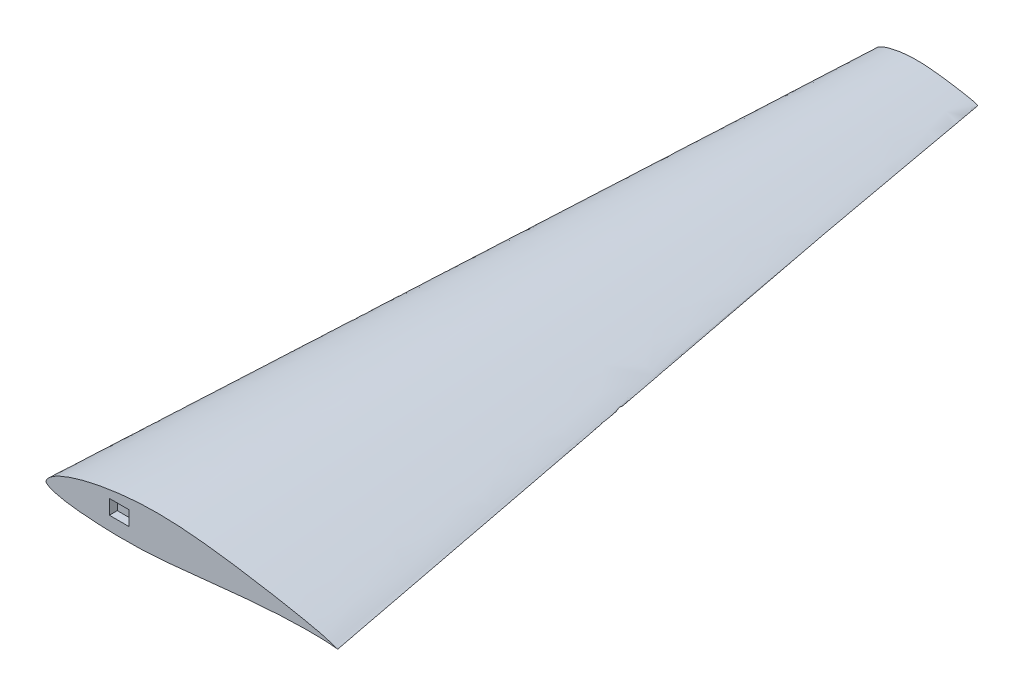
SolidWorks part; units mm, degrees
ref_plane "Front Plane" through (0, 0, 0) normal (0, 0, 1) x (1, 0, 0)
ref_plane "Top Plane" through (0, 0, 0) normal (0, 1, 0) x (1, 0, 0)
ref_plane "Right Plane" through (0, 0, 0) normal (1, 0, 0) x (0, 0, -1)
curve "Curve1"
  spline degree 3 poles (0.9921, 0.0008, 0) (1.0019, -0.0008, 0) (0.9929, 0.0016, 0) (0.9861, 0.0043, 0) (0.9706, 0.0096, 0) (0.9519, 0.0152, 0) (0.9278, 0.021, 0) (0.8992, 0.0273, 0) (0.8662, 0.0341, 0) (0.8293, 0.0413, 0) (0.789, 0.0488, 0) (0.746, 0.0564, 0) (0.7007, 0.0641, 0) (0.6538, 0.0714, 0) (0.6058, 0.0784, 0) (0.5573, 0.0846, 0) (0.5088, 0.0898, 0) (0.4609, 0.0938, 0) (0.4138, 0.0961, 0) (0.3679, 0.0966, 0) (0.3232, 0.0952, 0) (0.2801, 0.092, 0) (0.2388, 0.0874, 0) (0.1997, 0.0815, 0) (0.1631, 0.0746, 0) (0.1296, 0.0669, 0) (0.0993, 0.0585, 0) (0.0726, 0.0496, 0) (0.0499, 0.0404, 0) (0.0312, 0.031, 0) (0.0168, 0.0217, 0) (0.0085, 0.0145, 0) (0.0039, 0.009, 0) (0.0018, 0.0058, 0) (0.0004, 0.0024, 0) (0, 0.0003, 0) (0, -0.0012, 0) (0.0006, -0.0026, 0) (0.002, -0.0043, 0) (0.0049, -0.007, 0) (0.0107, -0.0108, 0) (0.0215, -0.0156, 0) (0.0378, -0.0206, 0) (0.0598, -0.0253, 0) (0.0864, -0.0294, 0) (0.1174, -0.033, 0) (0.1523, -0.036, 0) (0.1908, -0.0383, 0) (0.2323, -0.0397, 0) (0.2764, -0.0402, 0) (0.3228, -0.0395, 0) (0.3711, -0.0373, 0) (0.4212, -0.0335, 0) (0.4729, -0.0284, 0) (0.526, -0.0227, 0) (0.5798, -0.0169, 0) (0.6336, -0.0114, 0) (0.6866, -0.0064, 0) (0.7378, -0.0023, 0) (0.7866, 0.0009, 0) (0.832, 0.0031, 0) (0.8733, 0.0042, 0) (0.9096, 0.0045, 0) (0.9406, 0.0038, 0) (0.9645, 0.0029, 0) (0.984, 0.0013, 0) (0.9921, 0.0008, 0) (1.0019, -0.0008, 0) (0.9929, 0.0016, 0) knots -0.016161 -0.007282 -0.001839 0 0.00178 0.006777 0.014308 0.024046 0.036116 0.050547 0.06713 0.085624 0.105767 0.127282 0.149864 0.17323 0.197069 0.221103 0.245052 0.268663 0.291773 0.314299 0.336178 0.357377 0.377792 0.397225 0.415489 0.432417 0.447849 0.461651 0.473687 0.483898 0.492263 0.498797 0.499955 0.502811 0.504371 0.50536 0.505925 0.506503 0.507535 0.509205 0.512345 0.517665 0.526422 0.537425 0.550643 0.565966 0.583206 0.602155 0.622587 0.644255 0.666998 0.690703 0.715307 0.740824 0.767084 0.793717 0.820331 0.846519 0.871863 0.895937 0.918335 0.938667 0.956573 0.971715 0.983839 0.992718 0.998161 1 1.00178 1.006777 1.014308 periodic
sketch "Sketch1" plane through (0, 0, 0) normal (0, 0, 1) x (1, 0, 0)
  line L0 (1122.2059, -30.8288) -> (-1162.7941, -35.0845) construction
  spline S1 degree 3 poles (1104.1363, -28.0222) (1126.6295, -31.7875) (1105.8826, -26.3024) (1090.4575, -20.1288) (1054.9513, -7.9956) (1012.296, 4.6638) (957.0478, 17.8508) (891.7164, 32.0367) (816.2153, 47.3864) (731.9108, 63.6705) (639.9041, 80.612) (541.5101, 97.9168) (438.0076, 115.0958) (330.7593, 131.7488) (221.0675, 147.3336) (110.2357, 161.251) (-0.493, 172.9975) (-110.0556, 181.8587) (-217.6516, 186.9061) (-322.6724, 187.859) (-424.6755, 184.4831) (-523.1626, 176.9995) (-617.5035, 166.1709) (-706.8843, 152.6667) (-790.3524, 136.737) (-867.0563, 118.889) (-936.2082, 99.5088) (-997.0691, 79.0242) (-1049.0447, 57.9028) (-1091.6336, 36.4479) (-1124.4686, 15.1943) (-1143.3869, -1.4067) (-1153.8659, -14.0298) (-1158.6984, -21.3016) (-1161.9612, -29.0988) (-1162.8988, -33.8887) (-1162.7223, -37.2464) (-1161.3764, -40.4052) (-1158.2301, -44.4654) (-1151.5185, -50.6376) (-1138.2079, -59.2164) (-1113.635, -70.0567) (-1076.2399, -81.3981) (-1026.0446, -92.1031) (-965.2298, -101.4019) (-894.4776, -109.4657) (-814.6314, -116.0953) (-726.7099, -121.1028) (-631.8133, -124.2931) (-530.9633, -125.2112) (-425.0342, -123.2363) (-314.6436, -117.9744) (-200.1569, -109.1265) (-81.9663, -97.1903) (39.2548, -83.9633) (162.1641, -70.4688) (285.0306, -57.6215) (406.0083, -46.0046) (523.1884, -36.2734) (634.6311, -28.7415) (738.3789, -23.5277) (832.7109, -20.7776) (915.5317, -20.0924) (986.36, -21.3847) (1040.9806, -23.338) (1085.6437, -26.9173) (1104.1363, -28.0222) (1126.6295, -31.7875) (1105.8826, -26.3024) knots -0.016161 -0.007282 -0.001839 0 0.00178 0.006777 0.014308 0.024046 0.036116 0.050547 0.06713 0.085624 0.105767 0.127282 0.149864 0.17323 0.197069 0.221103 0.245052 0.268663 0.291773 0.314299 0.336178 0.357377 0.377792 0.397225 0.415489 0.432417 0.447849 0.461651 0.473687 0.483898 0.492263 0.498797 0.499955 0.502811 0.504371 0.50536 0.505925 0.506503 0.507535 0.509205 0.512345 0.517665 0.526422 0.537425 0.550643 0.565966 0.583206 0.602155 0.622587 0.644255 0.666998 0.690703 0.715307 0.740824 0.767084 0.793717 0.820331 0.846519 0.871863 0.895937 0.918335 0.938667 0.956573 0.971715 0.983839 0.992718 0.998161 1 1.00178 1.006777 1.014308 only from (1122.2059, -30.8288) to (1122.2059, -30.8288)
  dimension "D1" = 2285
ref_plane "Plane1" through (0, 0, 6200) normal (0, 0, 1) x (1, 0, 0)
ref_plane "Plane3" through (0, -35.0845, 0) normal (0, 1, 0) x (1, 0, 0)
sketch "Sketch4" plane through (0, -35.0845, 0) normal (0, 1, 0) x (1, 0, 0)
  line L1 (1122.2059, 0) -> (-1162.7941, 0) construction
  line L2 (-172.1886, -6200) -> (172.1886, -6200) construction
  line L4 (-1162.7941, 0) -> (-862.7941, -6200)
sketch "Sketch5" plane through (0, 0, 6200) normal (0, 0, 1) x (1, 0, 0)
  line L0 (-62.749, -35.2354) -> (-862.7688, -35.3009) construction
  spline S1 degree 3 poles (-69.0897, -34.3504) (-61.22, -35.5469) (-68.4893, -33.741) (-73.9048, -31.6671) (-86.3598, -27.6181) (-101.3126, -23.4229) (-120.663, -19.1093) (-143.5377, -14.4998) (-169.9677, -9.5373) (-199.4749, -4.2947) (-231.6736, 1.1372) (-266.1033, 6.6624) (-302.3153, 12.1171) (-339.8318, 17.3686) (-378.1955, 22.2345) (-416.9483, 26.5125) (-455.6538, 30.0335) (-493.9373, 32.5536) (-531.5145, 33.7529) (-568.1715, 33.5367) (-603.7528, 31.8256) (-638.0855, 28.6992) (-670.9538, 24.4271) (-702.0769, 19.2472) (-731.124, 13.2516) (-757.8002, 6.6219) (-781.8329, -0.5031) (-802.9662, -7.9701) (-820.9952, -15.6131) (-835.7466, -23.3233) (-847.0949, -30.9123) (-853.6106, -36.8049) (-857.2018, -41.2651) (-858.8503, -43.8282) (-859.9483, -46.5664) (-860.2505, -48.243) (-860.1714, -49.4139) (-859.6851, -50.5093) (-858.5659, -51.9099) (-856.1913, -54.0289) (-851.5011, -56.9533) (-842.8685, -60.6082) (-829.7584, -64.3709) (-812.1844, -67.8447) (-790.9116, -70.7722) (-766.1771, -73.2167) (-738.2762, -75.1133) (-707.5656, -76.4015) (-674.4302, -77.0191) (-639.2289, -76.8125) (-602.2702, -75.5698) (-563.7715, -73.1566) (-523.8621, -69.4706) (-482.6761, -64.6873) (-440.4393, -59.4377) (-397.6147, -54.086) (-354.8016, -48.9603) (-312.6413, -44.2739) (-271.7964, -40.2655) (-232.9425, -37.0546) (-196.7619, -34.6929) (-163.8546, -33.2402) (-134.9538, -32.5684) (-110.2281, -32.6493) (-91.1554, -33.0456) (-75.5494, -34.0614) (-69.0897, -34.3504) (-61.22, -35.5469) (-68.4893, -33.741) knots -0.016161 -0.007282 -0.001839 0 0.00178 0.006777 0.014308 0.024046 0.036116 0.050547 0.06713 0.085624 0.105767 0.127282 0.149864 0.17323 0.197069 0.221103 0.245052 0.268663 0.291773 0.314299 0.336178 0.357377 0.377792 0.397225 0.415489 0.432417 0.447849 0.461651 0.473687 0.483898 0.492263 0.498797 0.499955 0.502811 0.504371 0.50536 0.505925 0.506503 0.507535 0.509205 0.512345 0.517665 0.526422 0.537425 0.550643 0.565966 0.583206 0.602155 0.622587 0.644255 0.666998 0.690703 0.715307 0.740824 0.767084 0.793717 0.820331 0.846519 0.871863 0.895937 0.918335 0.938667 0.956573 0.971715 0.983839 0.992718 0.998161 1 1.00178 1.006777 1.014308 only from (-62.7688, -35.2354) to (-62.7688, -35.2354)
  dimension "D1" = 800
loft "Loft5" add profiles "Sketch1", "Sketch5" connector at (-829.2128, 127.5517, 0) connector at (-729.5824, 13.4038, 6200)
sketch "Sketch9" plane through (0, 0, 0) normal (0, 0, -1) x (-1, 0, 0)
  line L1 (513.5943, 97.9459) -> (666.6195, 97.9459)
  line L2 (513.5943, 97.9459) -> (513.5943, -16.278)
  line L3 (513.5943, -16.278) -> (666.6195, -16.278)
  line L4 (666.6195, 97.9459) -> (666.6195, -16.278)
  line L5 (513.5943, 97.9459) -> (666.6195, -16.278) construction
  line L6 (513.5943, -16.278) -> (666.6195, 97.9459) construction
  point P0 (590.1069, 40.8339)
extrude "Boss-Extrude1" add sketch "Sketch9" along normal blind 30
mirror "Mirror3" about plane through (0, 0, -30) normal (0, 0, -1) of bodies 104
sketch "Sketch10" plane through (0, 0, 6200) normal (0, 0, 1) x (1, 0, 0)
  line L1 (1321.2817, -875.42) -> (-2414.7647, -875.42)
  line L2 (1321.2817, -875.42) -> (1321.2817, 875.42)
  line L3 (1321.2817, 875.42) -> (-2414.7647, 875.42)
  line L4 (-2414.7647, -875.42) -> (-2414.7647, 875.42)
  line L5 (1321.2817, -875.42) -> (-2414.7647, 875.42) construction
  line L6 (1321.2817, 875.42) -> (-2414.7647, -875.42) construction
  point P0 (-546.7415, 0)
extrude "Cut-Extrude1" cut sketch "Sketch10" against normal blind 6202
sketch "Sketch12" plane through (0, 0, -2) normal (0, 0, 1) x (1, 0, 0)
  line L4 (-666.6195, 97.9459) -> (-666.6195, -16.278)
  line L5 (-666.6195, -16.278) -> (-513.5943, -16.278)
  line L6 (-513.5943, -16.278) -> (-513.5943, 97.9459)
  line L7 (-513.5943, 97.9459) -> (-666.6195, 97.9459)
  line L8 (-666.6195, 97.9459) -> (-666.6195, -16.278)
  line L9 (-666.6195, -16.278) -> (-513.5943, -16.278)
  line L10 (-513.5943, -16.278) -> (-513.5943, 97.9459)
  line L11 (-513.5943, 97.9459) -> (-666.6195, 97.9459)
  dimension "D1" = 0
extrude "Cut-Extrude2" cut sketch "Sketch12" against normal blind 120
sketch "Sketch13" plane through (0, 0, -6260) normal (0, 0, -1) x (-1, 0, 0)
  line L0 (62.8334, -35.2498) -> (860.0501, -47.2458)
  spline S0 degree 3 poles (68.4893, -33.741) (61.22, -35.5469) (69.0897, -34.3504) (75.5494, -34.0614) (91.1554, -33.0456) (110.2281, -32.6493) (134.9538, -32.5684) (163.8546, -33.2402) (196.7619, -34.6929) (232.9425, -37.0546) (271.7964, -40.2655) (312.6413, -44.2739) (354.8016, -48.9603) (397.6147, -54.086) (440.4393, -59.4377) (482.6761, -64.6873) (523.8621, -69.4706) (563.7715, -73.1566) (602.2702, -75.5698) (639.2289, -76.8125) (674.4302, -77.0191) (707.5656, -76.4015) (738.2762, -75.1133) (766.1771, -73.2167) (790.9116, -70.7722) (812.1844, -67.8447) (829.7584, -64.3709) (842.8685, -60.6082) (851.5011, -56.9533) (856.1913, -54.0289) (858.5659, -51.9099) (859.6851, -50.5093) (860.1714, -49.4139) (860.2505, -48.243) (859.9483, -46.5664) (858.8503, -43.8282) (857.2018, -41.2651) (853.6106, -36.8049) (847.0949, -30.9123) (835.7466, -23.3233) (820.9952, -15.6131) (802.9662, -7.9701) (781.8329, -0.5031) (757.8002, 6.6219) (731.124, 13.2516) (702.0769, 19.2472) (670.9538, 24.4271) (638.0855, 28.6992) (603.7528, 31.8256) (568.1715, 33.5367) (531.5145, 33.7529) (493.9373, 32.5536) (455.6538, 30.0335) (416.9483, 26.5125) (378.1955, 22.2345) (339.8318, 17.3686) (302.3153, 12.1171) (266.1033, 6.6624) (231.6736, 1.1372) (199.4749, -4.2947) (169.9677, -9.5373) (143.5377, -14.4998) (120.663, -19.1093) (101.3126, -23.4229) (86.3598, -27.6181) (73.9048, -31.6671) (68.4893, -33.741) (61.22, -35.5469) (69.0897, -34.3504) knots -0.014308 -0.006777 -0.00178 0 0.001839 0.007282 0.016161 0.028285 0.043427 0.061333 0.081665 0.104063 0.128137 0.153481 0.179669 0.206283 0.232916 0.259176 0.284693 0.309297 0.333002 0.355745 0.377413 0.397845 0.416794 0.434034 0.449357 0.462575 0.473578 0.482335 0.487655 0.490795 0.492465 0.493497 0.494075 0.49464 0.495629 0.497189 0.500045 0.501203 0.507737 0.516102 0.526313 0.538349 0.552151 0.567583 0.584511 0.602775 0.622208 0.642623 0.663822 0.685701 0.708227 0.731337 0.754948 0.778897 0.802931 0.82677 0.850136 0.872718 0.894233 0.914376 0.93287 0.949453 0.963884 0.975954 0.985692 0.993223 0.99822 1 1.001839 1.007282 1.016161 only from (62.7688, -35.2354) to (62.7688, -35.2354) construction
